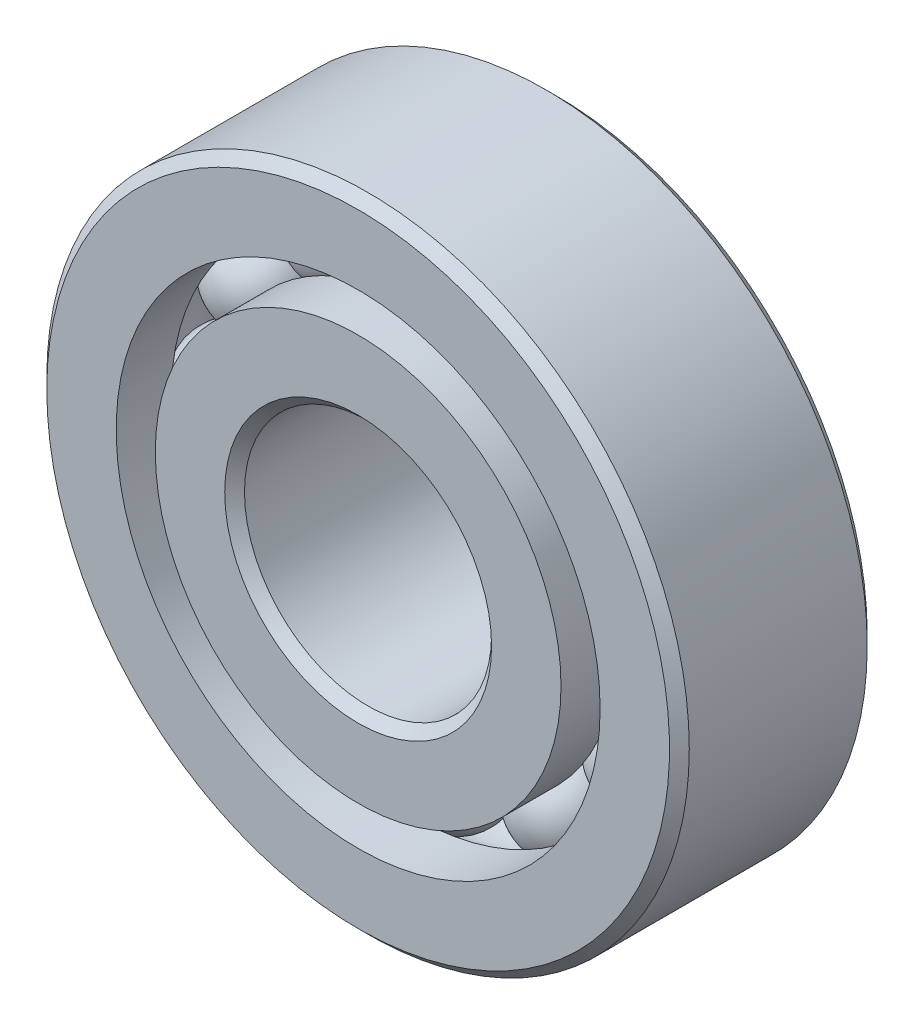
SolidWorks part; units mm, degrees
ref_plane "Front Plane" through (0, 0, 0) normal (0, 0, 1) x (1, 0, 0)
ref_plane "Top Plane" through (0, 0, 0) normal (0, 1, 0) x (1, 0, 0)
ref_plane "Right Plane" through (0, 0, 0) normal (1, 0, 0) x (0, 0, -1)
sketch "Sketch1" plane through (0, 0, 0) normal (1, 0, 0) x (0, 0, -1)
  line L0 (-4, 0) -> (4, 0) construction
  line L1 (0, 13) -> (0, -13) construction
  line L2 (3.6, 13) -> (-3.6, 13)
  line L3 (-3.6, 13) -> (-4, 12.6)
  line L4 (-4, 12.6) -> (-4, 9.7912)
  line L5 (-4, 9.7912) -> (-1.7778, 9.7912)
  line L6 (4, 9.7912) -> (1.7778, 9.7912)
  line L7 (4, 12.6) -> (4, 9.7912)
  line L8 (3.6, 13) -> (4, 12.6)
  line L9 (0, 13) -> (0, 9) construction
  line L10 (0, 9) -> (0, 5) construction
  arc A0 (-1.7778, 9.7912) -> (1.7778, 9.7912) centre (0, 9) cw
  point P14 (0, 5)
  dimension "Width" = 8
  dimension "OD" = 26
  dimension "D1" = 45
  dimension "D2" = 0.4
  dimension "Shaft Dia" = 10
  dimension "D3" = 3.5556
  dimension "D4" = 0.7912
revolve "Revolve1" add sketch "Sketch1" angle 360 about L0
sketch "Sketch3" plane through (0, 0, 0) normal (1, 0, 0) x (0, 0, -1)
  line L0 (-4, 8.2088) -> (-1.7778, 8.2088)
  line L1 (0, 13) -> (0, -13) construction
  line L2 (-4, 12.6) -> (-4, 9.7912) construction
  line L3 (-4, 8.2088) -> (-4, 5.4)
  line L4 (-3.6, 13) -> (-4, 12.6) construction
  line L5 (-4, 5.4) -> (-3.6, 5)
  line L6 (-3.6, 5) -> (3.6, 5)
  line L7 (3.6, 13) -> (3.6, -13) construction
  line L8 (3.6, 5) -> (4, 5.4)
  line L9 (4, -12.6) -> (4, 12.6) construction
  line L10 (4, 5.4) -> (4, 8.2088)
  line L11 (4, 8.2088) -> (1.7778, 8.2088)
  line L13 (3.6, 13) -> (4, 12.6) construction
  arc A0 (1.7778, 9.7912) -> (-1.7778, 9.7912) centre (0, 9) ccw construction
  arc A1 (1.7778, 8.2088) -> (-1.7778, 8.2088) centre (0, 9) cw
revolve "Revolve3" add sketch "Sketch3" angle 360 about L0
sketch "Sketch4" plane through (0, 0, 0) normal (1, 0, 0) x (0, 0, -1)
  line L0 (-1.9459, 9) -> (1.9459, 9)
  arc A2 (-1.9459, 9) -> (1.9459, 9) centre (0, 9) cw
  arc A3 (1.7778, 9.7912) -> (-1.7778, 9.7912) centre (0, 9) ccw construction
revolve "Revolve4" add sketch "Sketch4" angle 360 about L0
ref_axis "Axis1" through (0, 0, -4) along (0, 0, 1)
pattern_circular "CirPattern1" count 12 over 360 about axis through (0, 0, -4) along (0, 0, 1) of bodies 104
sketch "Sketch5" plane through (0, 0, 0) normal (1, 0, 0) x (0, 0, -1)
  line L0 (-4, 9.7912) -> (-1.7778, 9.7912) construction
  line L1 (-3.8, 9.7912) -> (-1.9459, 9.7912)
  line L2 (-3.8, 9.7912) -> (-3.8, 8.2088)
  line L3 (-3.8, 8.2088) -> (-1.9459, 8.2088)
  line L4 (-1.9459, 9.7912) -> (-1.9459, 8.2088)
  line L5 (-4, 8.2088) -> (-1.7778, 8.2088) construction
  line L6 (4, 9.7912) -> (1.7778, 9.7912) construction
  line L7 (3.8, 9.7912) -> (1.9459, 9.7912)
  line L8 (3.8, 9.7912) -> (3.8, 8.2088)
  line L9 (3.8, 8.2088) -> (1.9459, 8.2088)
  line L10 (1.9459, 9.7912) -> (1.9459, 8.2088)
  line L11 (4, 8.2088) -> (1.7778, 8.2088) construction
  line L12 (-3.6, 13) -> (-4, 12.6) construction
  point P18 (-3.8, 12.8)
equation "\"D2@Sketch1\" = \"Width@Sketch1\"*.05"
equation "\"D3@Sketch1\" = \"Width@Sketch1\"/2.25"
equation "\"D4@Sketch1\" = (((\"OD@Sketch1\"-\"Width@Sketch1\")/2)/3.25)/3.5"
equation "\"D2@CirPattern1\" = 360/\"Balls@CirPattern1\""
